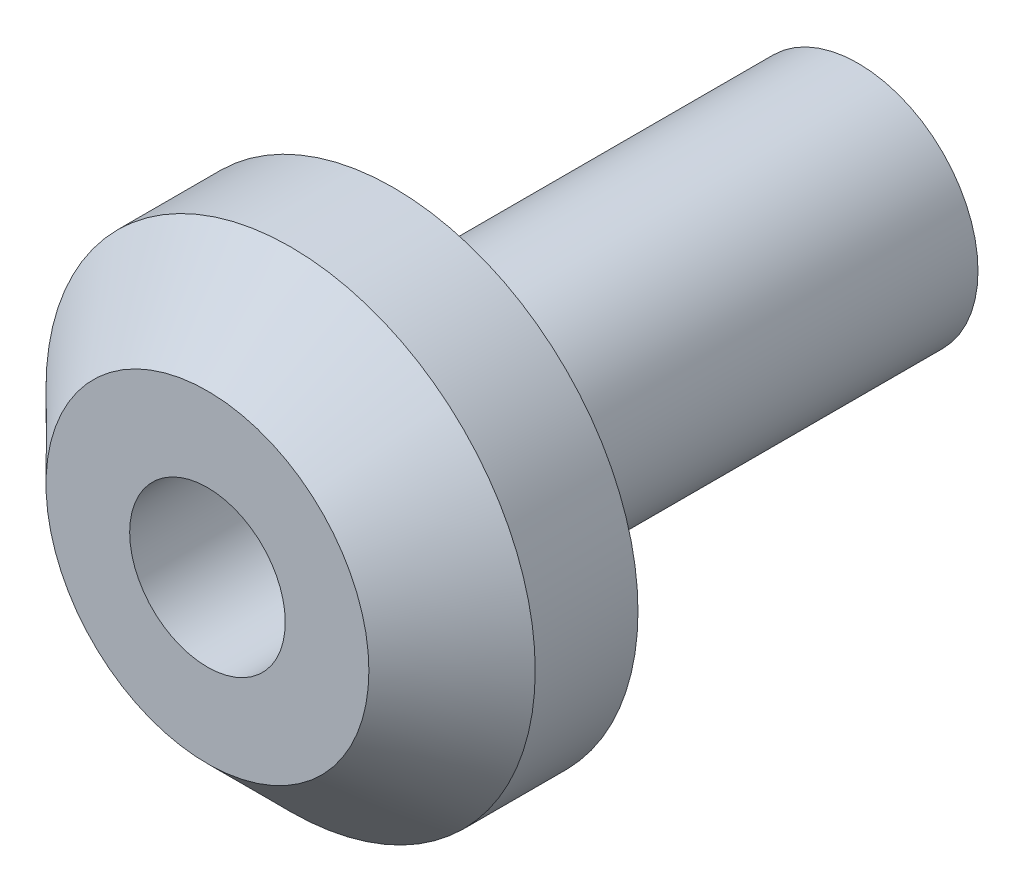
SolidWorks part; units mm, degrees
material "Brass"
ref_plane "Front Plane" through (0, 0, 0) normal (0, 0, 1) x (1, 0, 0)
ref_plane "Top Plane" through (0, 0, 0) normal (0, 1, 0) x (1, 0, 0)
ref_plane "Right Plane" through (0, 0, 0) normal (1, 0, 0) x (0, 0, -1)
sketch "Sketch1" plane through (0, 0, 0) normal (0, 0, 1) x (1, 0, 0)
  circle A0 centre (0, 0) radius 4.0386
  circle A1 centre (0, 0) radius 12.7
extrude "Boss-Extrude1" add sketch "Sketch1" along normal blind 9.652
sketch "Sketch2" plane through (0, 0, 0) normal (0, 0, -1) x (-1, 0, 0)
  circle A0 centre (0, 0) radius 4.0386
  circle A1 centre (0, 0) radius 6.223
extrude "Boss-Extrude2" add sketch "Sketch2" along normal blind 24.13
chamfer "Chamfer1" distance 4.318 angle 45 1 edges at (12.7, 0, 9.652)
